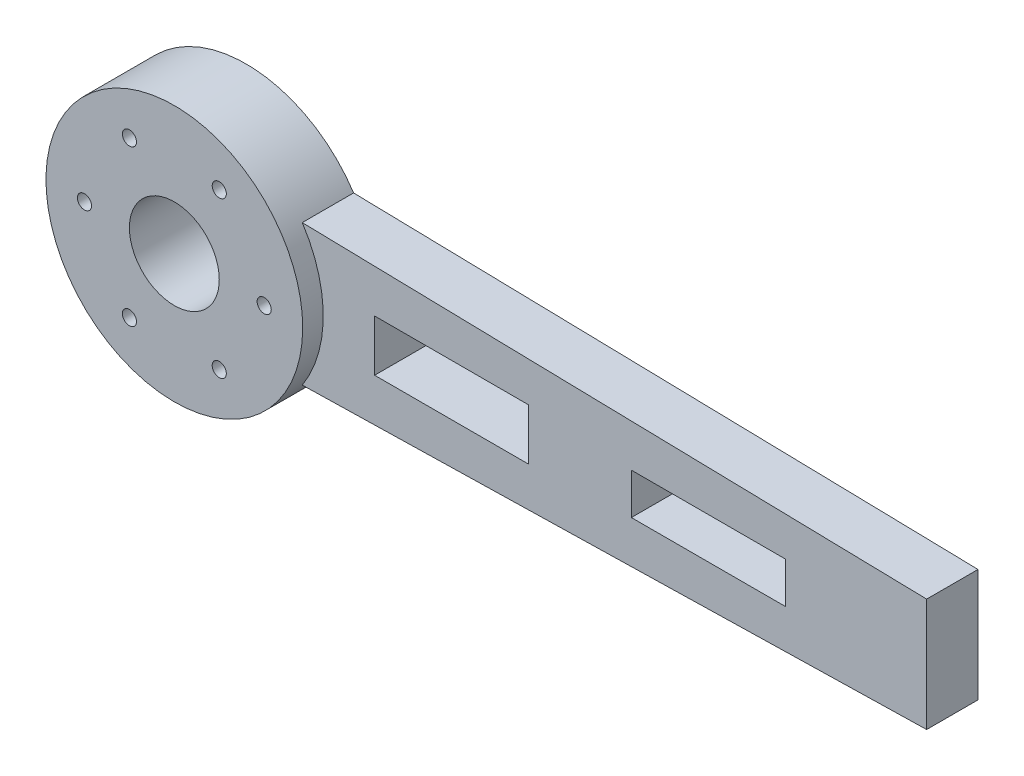
SolidWorks part; units mm, degrees
ref_plane "Front Plane" through (0, 0, 0) normal (0, 0, 1) x (1, 0, 0)
ref_plane "Top Plane" through (0, 0, 0) normal (0, 1, 0) x (1, 0, 0)
ref_plane "Right Plane" through (0, 0, 0) normal (1, 0, 0) x (0, 0, -1)
sketch "Sketch1" plane through (0, 0, 0) normal (0, 0, 1) x (1, 0, 0)
  circle A0 centre (0, 0) radius 50
  circle A1 centre (0, 0) radius 17.5
  circle A2 centre (35, 0) radius 2.75
  circle A3 centre (17.5, 30.3109) radius 2.75
  circle A4 centre (-17.5, 30.3109) radius 2.75
  circle A5 centre (-35, 0) radius 2.75
  circle A6 centre (-17.5, -30.3109) radius 2.75
  circle A7 centre (17.5, -30.3109) radius 2.75
extrude "Boss-Extrude1" add sketch "Sketch1" along normal blind 28
sketch "Sketch2" plane through (0, 0, 0) normal (0, 0, 1) x (1, 0, 0)
  circle A0 centre (300, 0) radius 35
  circle A1 centre (300, 0) radius 7
  circle A2 centre (322.5, 0) radius 2.75
  circle A3 centre (300, 22.5) radius 2.75
  circle A4 centre (277.5, 0) radius 2.75
  circle A5 centre (300, -22.5) radius 2.75
  circle A6 centre (300, 22.5) radius 2.75
sketch "Sketch3" plane through (0, 0, 0) normal (0, 0, 1) x (1, 0, 0)
  line L0 (15, -28) -> (15, 28)
  line L1 (15, 28) -> (285, 22)
  line L2 (285, 22) -> (285, -22)
  line L3 (285, -22) -> (15, -28)
  line L5 (70, -10) -> (130, -10)
  line L6 (70, -10) -> (70, 10)
  line L7 (70, 10) -> (130, 10)
  line L8 (130, -10) -> (130, 10)
  line L9 (70, -10) -> (130, 10) construction
  line L10 (70, 10) -> (130, -10) construction
  line L11 (170, -8) -> (230, -8)
  line L12 (170, -8) -> (170, 8)
  line L13 (170, 8) -> (230, 8)
  line L14 (230, -8) -> (230, 8)
  line L15 (170, -8) -> (230, 8) construction
  line L16 (170, 8) -> (230, -8) construction
  point P4 (100, 0)
  point P9 (200, 0)
extrude "Boss-Extrude3" add sketch "Sketch3" along normal blind 20
ref_axis "Axis1" through (0, 0, -1.4) along (0, 0, 1)
ref_plane "Wrist Plane" through (300, 0, 0) normal (1, 0, 0) x (0, 0, -1)
ref_axis "Axis2" through (300, 0, -1.4) along (0, 0, 1)
sketch3d "3DSketch1"
  point P0 (300, 0, 24)
